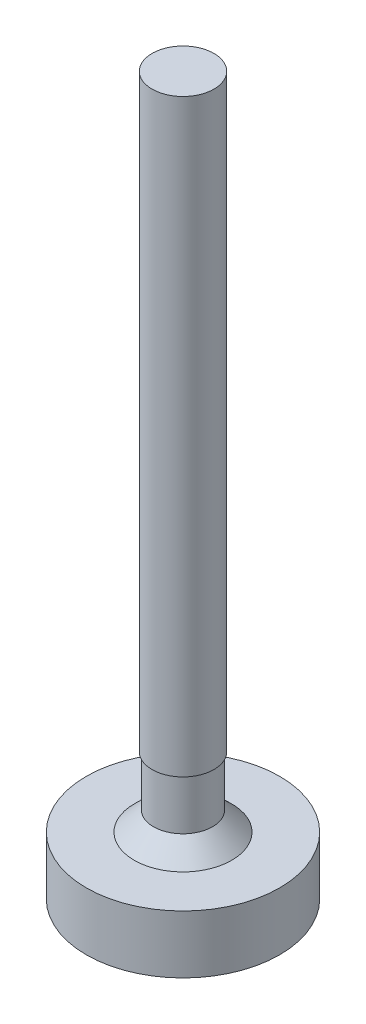
SolidWorks part; units mm, degrees
ref_plane "前视基准面" through (0, 0, 0) normal (0, 0, 1) x (1, 0, 0)
ref_plane "上视基准面" through (0, 0, 0) normal (0, 1, 0) x (1, 0, 0)
ref_plane "右视基准面" through (0, 0, 0) normal (1, 0, 0) x (0, 0, -1)
sketch "草图1" plane through (0, 0, 0) normal (0, 1, 0) x (1, 0, 0)
  circle A0 centre (0, 0) radius 5
  circle A1 centre (0, 0) radius 1.6
  circle A2 centre (0, 0) radius 1.525
  dimension "D1" = 10
  dimension "D2" = 3.2
  dimension "D3" = 3.05
extrude "凸台-拉伸1" add sketch "草图1" along normal blind 3 contours A0
extrude "凸台-拉伸2" add sketch "草图1<3>" along normal blind 3.6 from surface contours A2 starting at face at (0, 3, 5)
sketch "草图1<3>" plane through (0, 0, 0) normal (0, 1, 0) x (1, 0, 0) same geometry as "草图1"
extrude "凸台-拉伸3" add sketch "草图1<4>" along normal blind 30.48 from surface contours A1 starting at face at (0, 6.6, 1.525)
sketch "草图1<4>" plane through (0, 0, 0) normal (0, 1, 0) x (1, 0, 0) same geometry as "草图1"
chamfer "倒角1" distance 1 angle 45 1 edges at (0, 3, 1.525)
